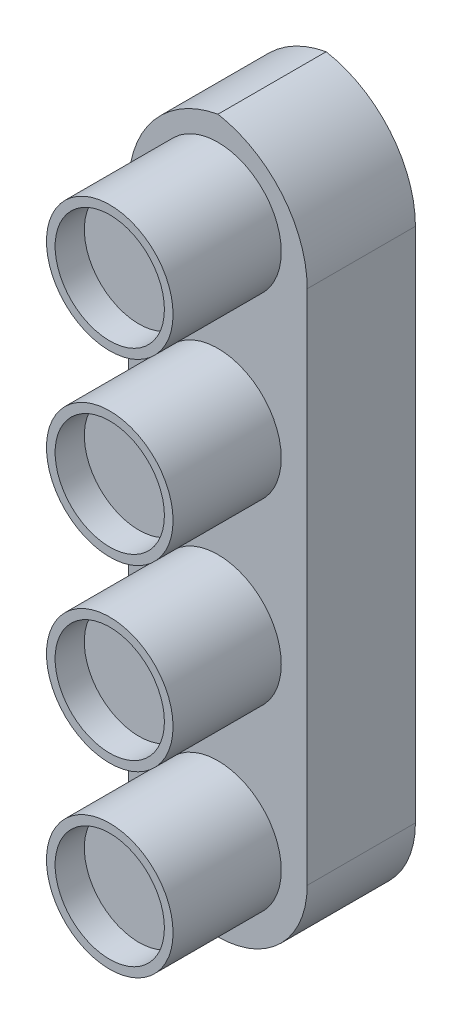
SolidWorks part; units mm, degrees
ref_plane "Ebene vorne" through (0, 0, 0) normal (0, 0, 1) x (1, 0, 0)
ref_plane "Ebene oben" through (0, 0, 0) normal (0, 1, 0) x (1, 0, 0)
ref_plane "Ebene rechts" through (0, 0, 0) normal (1, 0, 0) x (0, 0, -1)
sketch "Sketch1" plane through (0, 0, 0) normal (0, 0, 1) x (1, 0, 0)
  line L1 (0, 0) -> (-165, 0) construction
  line L2 (0, 0) -> (0, 165) construction
  line L3 (0, 165) -> (-165, 165) construction
  line L4 (-165, 0) -> (-165, 165) construction
  line L9 (-129.084, 165) -> (-112.584, 165)
  line L10 (-129.084, 165) -> (-129.084, 99)
  line L11 (-129.084, 99) -> (-112.584, 99)
  line L12 (-112.584, 165) -> (-112.584, 99)
  dimension "D1" = 165
  dimension "D2" = 165
  dimension "D5" = 66
  dimension "D6" = 16.5
extrude "Boss-Extrude1" add sketch "Sketch1" along normal blind 20
sketch "Sketch2" plane through (0, 0, 20) normal (0, 0, 1) x (1, 0, 0)
  line L1 (-129.084, 132) -> (-112.584, 132) construction
  line L2 (-129.084, 165) -> (-129.084, 99) construction
  line L3 (-112.584, 99) -> (-112.584, 165) construction
  line L5 (-129.084, 165) -> (-112.584, 165)
  line L6 (-129.084, 165) -> (-129.084, 99)
  line L7 (-129.084, 99) -> (-112.584, 99)
  line L8 (-112.584, 165) -> (-112.584, 99)
  circle A2 centre (-120.834, 156.75) radius 5.85
  circle A3 centre (-120.834, 140.25) radius 5.85
  circle A4 centre (-120.834, 156.75) radius 5.05
  circle A5 centre (-120.834, 140.25) radius 5.05
  circle A6 centre (-120.834, 123.75) radius 5.05
  circle A7 centre (-120.834, 123.75) radius 5.85
  circle A8 centre (-120.834, 107.25) radius 5.85
  circle A9 centre (-120.834, 107.25) radius 5.05
  point P11 (-120.834, 132)
  line M4 (-129.084, 165) -> (-129.084, 99)
  line M5 (-129.084, 99) -> (-112.584, 99)
  line M6 (-112.584, 99) -> (-112.584, 165)
  line M7 (-112.584, 165) -> (-129.084, 165)
  dimension "D1" = 8.25
  dimension "D2" = 16.5
  dimension "D3" = 11.7
  dimension "D4" = 11.7
  dimension "D5" = 10.1
  dimension "D6" = 10.1
extrude "Cut-Extrude1" cut sketch "Sketch2" against normal blind 10 contours L1 L6 A7 A8 M5 M6 | L1 L8 A3 A2 M4 M7 | A5 | A6 | A9 | A4 region at (-120.834, 148.5, 20) region at (-120.834, 115.5, 20) region at (-120.834, 156.75, 20) region at (-120.834, 140.25, 20) region at (-120.834, 123.75, 20) region at (-120.834, 107.25, 20)
fillet "Fillet1" radius 10 2 edges at (-129.084, 165, 5) (-112.584, 165, 5)
fillet "Fillet2" radius 8.25 2 edges at (-129.084, 99, 5) (-112.584, 99, 5)
sketch "Sketch3" plane through (0, 0, 0) normal (0, 0, -1) x (-1, 0, 0)
  line L6 (120.834, 165) -> (120.834, 99) construction
  line L9 (112.584, 132) -> (129.084, 132) construction
  line L10 (112.584, 107.25) -> (112.584, 155) construction
  line L11 (129.084, 155) -> (129.084, 107.25) construction
  line L12 (129.084, 165) -> (112.584, 165) construction
  line L13 (129.084, 99) -> (112.584, 99) construction
  circle A0 centre (120.834, 156.75) radius 2.5
  circle A1 centre (120.834, 140.25) radius 2.5
  circle A4 centre (120.834, 123.75) radius 2.5
  circle A5 centre (120.834, 107.25) radius 2.5
  point P14 (120.834, 132)
  point P15 (120.834, 132)
  dimension "D1" = 8.25
  dimension "D3" = 5
  dimension "D4" = 5
  dimension "D2" = 16.5
extrude "Cut-Extrude2" [suppressed] cut sketch "Sketch3" against normal blind 5
sketch "Skizze1" plane through (0, 0, 10) normal (0, 0, 1) x (1, 0, 0)
  circle A0 centre (-120.834, 156.75) radius 5.1
  circle A1 centre (-120.834, 140.25) radius 5.1
  circle A2 centre (-120.834, 123.75) radius 5.1
  circle A3 centre (-120.834, 107.25) radius 5.1
  dimension "D1" = 10.2
  dimension "D2" = 10.2
  dimension "D3" = 10.2
  dimension "D4" = 10.2
extrude "Aufsatz-Linear austragen1" add sketch "Skizze1" along normal blind 7.3
sketch "Skizze2" plane through (0, 0, 0) normal (0, 0, -1) x (-1, 0, 0)
  line L4 (127.084, 107.25) -> (127.084, 155)
  line L5 (114.584, 155) -> (114.584, 107.25)
  line L6 (127.084, 107.25) -> (127.084, 155)
  line L7 (114.584, 155) -> (114.584, 107.25)
  arc A8 (114.584, 107.25) -> (120.834, 101) centre (120.834, 107.25) ccw
  arc A9 (120.834, 101) -> (127.084, 107.25) centre (120.834, 107.25) ccw
  arc A10 (127.084, 155) -> (120.834, 162.8062) centre (119.084, 155) ccw
  arc A11 (120.834, 162.8062) -> (114.584, 155) centre (122.584, 155) ccw
  arc A12 (114.584, 107.25) -> (120.834, 101) centre (120.834, 107.25) ccw
  arc A13 (120.834, 101) -> (127.084, 107.25) centre (120.834, 107.25) ccw
  arc A14 (127.084, 155) -> (120.834, 162.8062) centre (119.084, 155) ccw
  arc A15 (120.834, 162.8062) -> (114.584, 155) centre (122.584, 155) ccw
  dimension "D1" = 2
extrude "Schnitt-Linear austragen1" cut sketch "Skizze2" against normal blind 9
